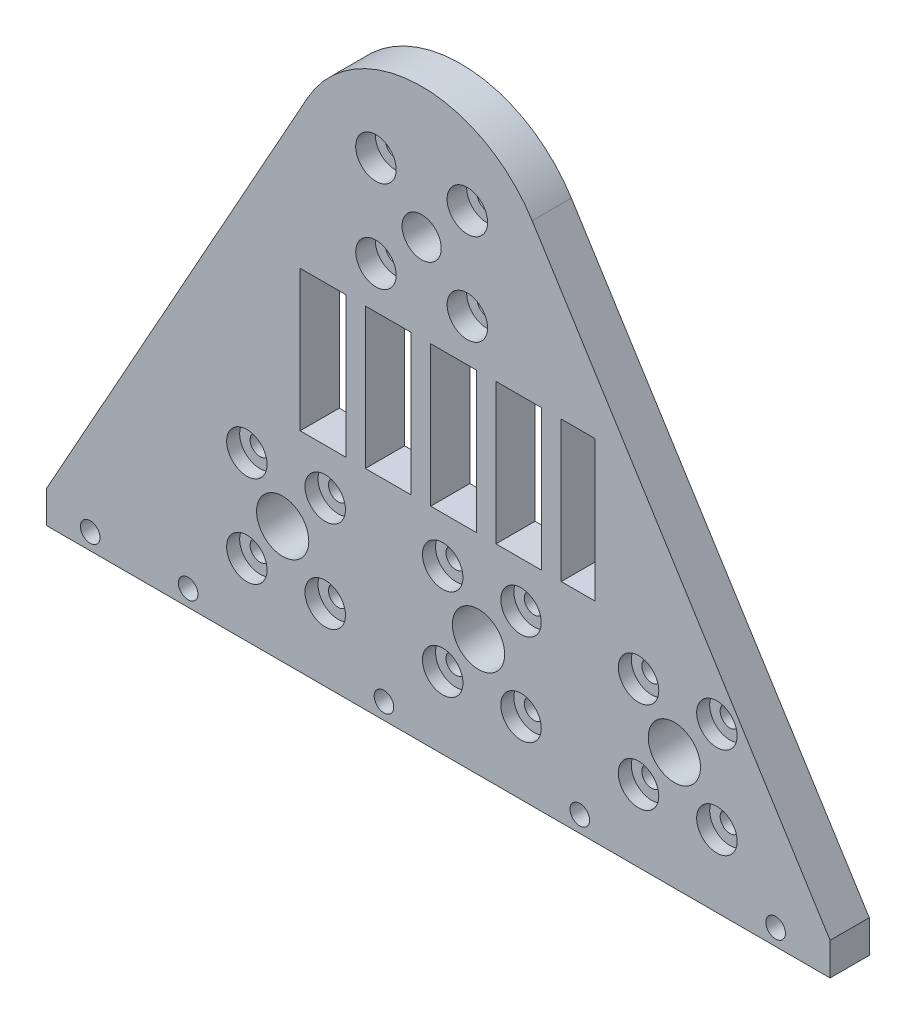
SolidWorks part; units mm, degrees
ref_plane "前视基准面" through (0, 0, 0) normal (0, 0, 1) x (1, 0, 0)
ref_plane "上视基准面" through (0, 0, 0) normal (0, 1, 0) x (1, 0, 0)
ref_plane "右视基准面" through (0, 0, 0) normal (1, 0, 0) x (0, 0, -1)
other "Configuration Table"
sketch "草图1" plane through (0, 0, 0) normal (0, 0, 1) x (1, 0, 0)
  line L5 (53.2118, 15.1053) -> (98.8463, -57.534)
  line L6 (18.8044, 14.1987) -> (-21.1537, -57.534)
  line L9 (98.8463, -57.534) -> (98.8463, -62.534)
  line L10 (98.8463, -62.534) -> (-21.1537, -62.534)
  line L11 (-21.1537, -62.534) -> (-21.1537, -57.534)
  arc A0 (53.2118, 15.1053) -> (18.8044, 14.1987) centre (36.2765, 4.466) ccw
  circle A2 centre (36.2765, 4.466) radius 3
  point P0 (0, 0)
extrude "凸台-拉伸1" add sketch "草图1" along normal blind 6
sketch "草图2" plane through (0, 0, 6) normal (0, 0, 1) x (1, 0, 0)
  line L0 (36.2765, 4.466) -> (36.2765, 16.549) construction
  line L5 (36.2765, 4.466) -> (44.4343, 4.466) construction
  circle A2 centre (29.2765, 11.466) radius 3.1
  circle A3 centre (43.2765, 11.466) radius 3.1
  circle A4 centre (43.2765, -2.534) radius 3.1
  circle A5 centre (29.2765, -2.534) radius 3.1
extrude "切除-拉伸6" cut sketch "草图2" against normal blind 3
sketch "草图4" plane through (0, 0, 3) normal (0, 0, 1) x (1, 0, 0)
  circle A0 centre (43.2765, 11.466) radius 1.5 construction
  circle A1 centre (43.2765, 11.466) radius 1.5
  circle A2 centre (43.2765, -2.534) radius 1.5 construction
  circle A3 centre (43.2765, -2.534) radius 1.5
  circle A4 centre (29.2765, -2.534) radius 1.5 construction
  circle A5 centre (29.2765, -2.534) radius 1.5
  circle A6 centre (29.2765, 11.466) radius 1.5 construction
  circle A7 centre (29.2765, 11.466) radius 1.5
extrude "切除-拉伸7" cut sketch "草图4" against normal through all
sketch "草图5" plane through (0, 0, 6) normal (0, 0, 1) x (1, 0, 0)
  line L0 (24.6608, -8.9774) -> (24.6608, -30.534)
  line L1 (14.6608, -8.9774) -> (62.8566, -8.9774)
  line L2 (14.6608, -8.9774) -> (14.6608, -30.534)
  line L3 (14.6608, -30.534) -> (62.8566, -30.534)
  line L4 (62.8566, -8.9774) -> (62.8566, -30.534)
  line L5 (14.6608, -8.9774) -> (17.6608, -8.9774)
  line L6 (14.6608, -8.9774) -> (14.6608, -30.534)
  line L7 (14.6608, -30.534) -> (17.6608, -30.534)
  line L8 (17.6608, -8.9774) -> (17.6608, -30.534)
  line L9 (24.6608, -8.9774) -> (27.6608, -8.9774)
  line L10 (27.6608, -8.9774) -> (27.6608, -30.534)
  line L11 (24.6608, -30.534) -> (27.6608, -30.534)
  line L12 (34.6608, -8.9774) -> (34.6608, -30.534)
  line L13 (34.6608, -8.9774) -> (37.6608, -8.9774)
  line L14 (37.6608, -8.9774) -> (37.6608, -30.534)
  line L15 (34.6608, -30.534) -> (37.6608, -30.534)
  line L16 (44.6608, -8.9774) -> (44.6608, -30.534)
  line L17 (44.6608, -8.9774) -> (47.6608, -8.9774)
  line L18 (47.6608, -8.9774) -> (47.6608, -30.534)
  line L19 (44.6608, -30.534) -> (47.6608, -30.534)
  line L20 (54.6608, -8.9774) -> (54.6608, -30.534)
  line L21 (54.6608, -8.9774) -> (57.6608, -8.9774)
  line L22 (57.6608, -8.9774) -> (57.6608, -30.534)
  line L23 (54.6608, -30.534) -> (57.6608, -30.534)
  circle A0 centre (36.2765, 4.466) radius 22 construction
  circle A1 centre (14.9882, -44.534) radius 4 construction
  circle A2 centre (14.9882, -44.534) radius 4
  circle A3 centre (44.9882, -44.534) radius 4 construction
  circle A4 centre (44.9882, -44.534) radius 4
  circle A5 centre (74.9882, -44.534) radius 4 construction
  circle A6 centre (74.9882, -44.534) radius 4
  dimension "D1" = 3
  dimension "D3" = 5.1958
  dimension "D4" = 35
  dimension "D2" = 5
extrude "切除-拉伸8" cut sketch "草图5" against normal up to next contours L1 L8 L3 L0 | L12 L1 L10 L3 | L16 L1 L14 L3 | L20 L1 L18 L3 | L1 L22 L3 L4 | A2 | A4 | A6 region at (21.1608, -19.7557, 6) region at (31.1608, -19.7557, 6) region at (41.1608, -19.7557, 6) region at (51.1608, -19.7557, 6) region at (60.2587, -19.7557, 6) region at (14.9882, -44.534, 6) region at (44.9882, -44.534, 6) region at (74.9882, -44.534, 6)
sketch "草图6" plane through (0, 0, 6) normal (0, 0, 1) x (1, 0, 0)
  circle A0 centre (21.5023, -37.534) radius 3.1
  circle A1 centre (9.5023, -37.534) radius 3.1
  circle A2 centre (9.5023, -51.534) radius 3.1
  circle A3 centre (21.5023, -51.534) radius 3.1
  circle A4 centre (39.5023, -37.534) radius 3.1
  circle A5 centre (51.5023, -37.534) radius 3.1
  circle A6 centre (51.5023, -51.534) radius 3.1
  circle A7 centre (39.5023, -51.534) radius 3.1
  circle A8 centre (69.5023, -37.534) radius 3.1
  circle A9 centre (81.5023, -37.534) radius 3.1
  circle A10 centre (81.5023, -51.534) radius 3.1
  circle A11 centre (69.5023, -51.534) radius 3.1
  dimension "D1" = 3
extrude "切除-拉伸9" cut sketch "草图6" against normal blind 2
sketch "草图7" plane through (0, 0, 4) normal (0, 0, 1) x (1, 0, 0)
  circle A0 centre (9.5023, -37.534) radius 1.5
  circle A1 centre (21.5023, -37.534) radius 1.5
  circle A2 centre (9.5023, -51.534) radius 1.5
  circle A3 centre (21.5023, -51.534) radius 1.5
  circle A4 centre (51.5023, -51.534) radius 1.5
  circle A5 centre (39.5023, -51.534) radius 1.5
  circle A6 centre (39.5023, -37.534) radius 1.5
  circle A7 centre (51.5023, -37.534) radius 1.5
  circle A8 centre (81.5023, -51.534) radius 1.5
  circle A9 centre (69.5023, -51.534) radius 1.5
  circle A10 centre (69.5023, -37.534) radius 1.5
  circle A11 centre (81.5023, -37.534) radius 1.5
extrude "切除-拉伸10" cut sketch "草图7" against normal through all
sketch "草图8" plane through (0, 0, 6) normal (0, 0, 1) x (1, 0, 0)
  circle A0 centre (90.5023, -60.034) radius 1.5 construction
  circle A1 centre (90.5023, -60.034) radius 1.5
  circle A2 centre (60.5023, -60.034) radius 1.5 construction
  circle A3 centre (60.5023, -60.034) radius 1.5
  circle A4 centre (30.5023, -60.034) radius 1.5 construction
  circle A5 centre (30.5023, -60.034) radius 1.5
  circle A6 centre (0.5023, -60.034) radius 1.5 construction
  circle A7 centre (0.5023, -60.034) radius 1.5
  circle A8 centre (-14.4977, -60.034) radius 1.5 construction
  circle A9 centre (-14.4977, -60.034) radius 1.5
extrude "切除-拉伸11" cut sketch "草图8" against normal through all
